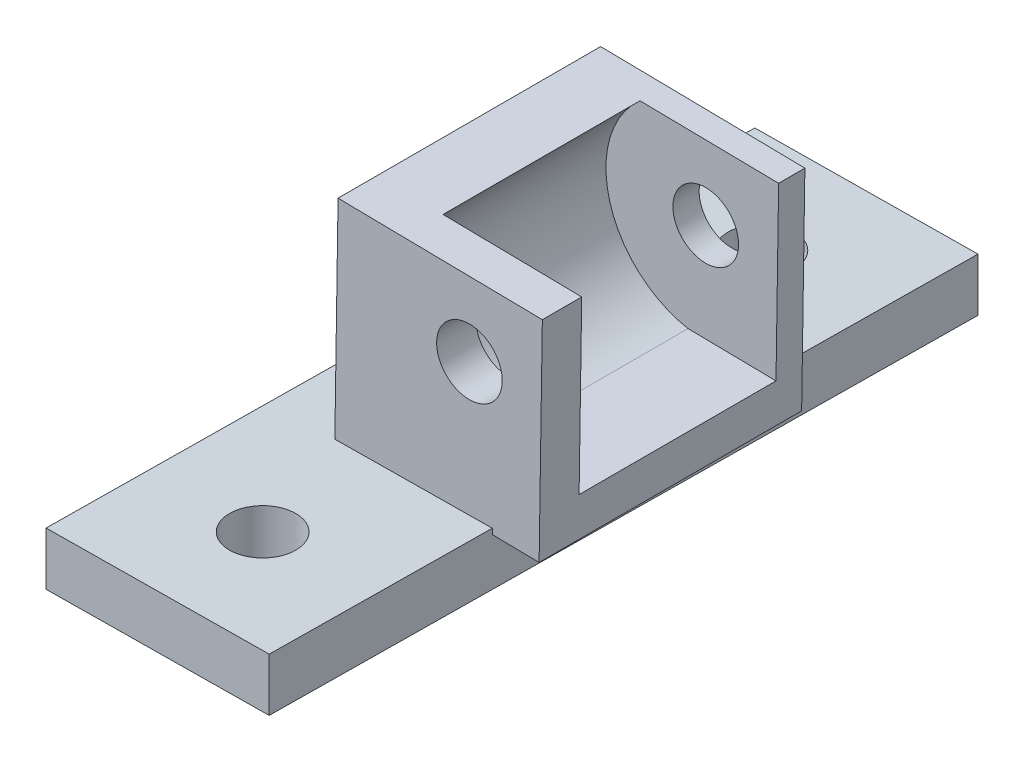
SolidWorks part; units mm, degrees
ref_plane "Front Plane" through (0, 0, 0) normal (0, 0, 1) x (1, 0, 0)
ref_plane "Top Plane" through (0, 0, 0) normal (0, 1, 0) x (1, 0, 0)
ref_plane "Right Plane" through (0, 0, 0) normal (1, 0, 0) x (0, 0, -1)
sketch "Sketch1" plane through (0, 0, 0) normal (0, 0, 1) x (1, 0, 0)
  line L0 (-620.8374, 110.7203) -> (-621.1503, 90.2249)
  line L1 (-604.7125, 110.4741) -> (-634.2525, 110.9251) construction
  line L2 (-621.1503, 90.2249) -> (-640.9147, 90.5267)
  line L3 (-640.9147, 90.5267) -> (-640.6018, 111.0221)
  line L4 (-640.6018, 111.0221) -> (-620.8374, 110.7203)
  line L5 (-606.4491, 93.8109) -> (-629.5989, 94.1643) construction
  line L6 (-606.4491, 93.8109) -> (-629.5989, 94.1643)
  arc A0 (-634.2525, 110.9251) -> (-634.4712, 96.6012) centre (-627.8931, 103.6644) ccw construction
  arc A1 (-634.4712, 96.6012) -> (-629.5989, 94.1643) centre (-627.8931, 103.6644) ccw construction
  arc A2 (-634.2525, 110.9251) -> (-634.4712, 96.6012) centre (-627.8931, 103.6644) ccw
  arc A3 (-634.4712, 96.6012) -> (-629.5989, 94.1643) centre (-627.8931, 103.6644) ccw
  dimension "D1" = 3.81
  dimension "D2" = 6.35
  dimension "D3" = 19.7667
extrude "Boss-Extrude1" add sketch "Sketch1" against normal blind 21.59 contours A3 A2 L4 L3 L2 L0 L6 region at (-621.4085, 92.1341, 0)
sketch "Sketch2" plane through (0, 0, -19.05) normal (0, 0, -1) x (-1, 0, 0)
  line L0 (621.0921, 94.0345) -> (620.8374, 110.7203)
  line L1 (604.6203, 110.4727) -> (634.2525, 110.9251) construction
  line L2 (620.8374, 110.7203) -> (634.2525, 110.9251)
  line L3 (621.0921, 94.0345) -> (629.5989, 94.1643) construction
  line L4 (621.0921, 94.0345) -> (629.5989, 94.1643)
  line L5 (621.0921, 94.0345) -> (629.5989, 94.1643)
  circle A0 centre (627.8931, 103.6644) radius 3.175 construction
  arc A1 (629.5989, 94.1643) -> (634.2525, 110.9251) centre (627.8931, 103.6644) ccw construction
  circle A2 centre (627.8931, 103.6644) radius 3.175
  arc A3 (629.5989, 94.1643) -> (634.2525, 110.9251) centre (627.8931, 103.6644) ccw
  circle M6 centre (627.8931, 103.6644) radius 3.175
  line M7 (604.4767, 96.1432) -> (634.4712, 96.6012)
  arc M8 (634.4712, 96.6012) -> (634.2525, 110.9251) centre (627.8931, 103.6644) ccw
  line M9 (634.2525, 110.9251) -> (604.6203, 110.4727)
extrude "Boss-Extrude3" add sketch "Sketch2" along normal up to surface (2.54 mm away) contours L0 M7 M8 M9 M6 | L4 A3 L0 M7 region at (-626.9307, 95.381, -19.05) region at (-621.1681, 103.5617, -19.05) up to face at (-632.1463, 98.2392, -21.59)
sketch "Sketch3" plane through (0, 0, 0) normal (0, 0, 1) x (1, 0, 0)
  line L0 (-640.6018, 111.0221) -> (-620.8374, 110.7203)
  line L1 (-620.8374, 110.7203) -> (-621.1503, 90.2249)
  line L2 (-621.1503, 90.2249) -> (-640.9147, 90.5267)
  line L3 (-640.9147, 90.5267) -> (-640.6018, 111.0221)
  circle A0 centre (-627.8931, 103.6644) radius 3.175
  dimension "D1" = 6.35
extrude "Boss-Extrude4" add sketch "Sketch3" along normal blind 3.81 contours L3 L0 L1 L2 | A0
ref_plane "Plane1" through (-1.0096, 97.2566, -1.0889) normal (-0.0104, 0.9999, -0.0112) x (0.9999, 0.0104, -0.0001)
sketch "Sketch4" plane through (-1.0096, 97.2566, -1.0889) normal (-0.0104, 0.9999, -0.0112) x (0.9999, 0.0104, -0.0001)
  line L1 (-646.2911, 42.1652) -> (-624.7011, 42.1652)
  line L2 (-646.2911, 42.1652) -> (-646.2911, -26.4132)
  line L3 (-646.2911, -26.4132) -> (-624.7011, -26.4132)
  line L4 (-624.7011, 42.1652) -> (-624.7011, -26.4132)
  circle A0 centre (-635.4961, -16.2532) radius 3.175
  circle A1 centre (-635.4961, 32.0052) radius 3.175
  dimension "D7" = 10.795
  dimension "D9" = 6.35
  dimension "D10" = 6.35
  dimension "D1" = 6.35
  dimension "D2" = 21.59
  dimension "D3" = 21.59
  dimension "D4" = 21.59
  dimension "D5" = 10.16
  dimension "D6" = 10.795
  dimension "D8" = 10.16
extrude "Boss-Extrude5" add sketch "Sketch4" against normal blind 5.08
